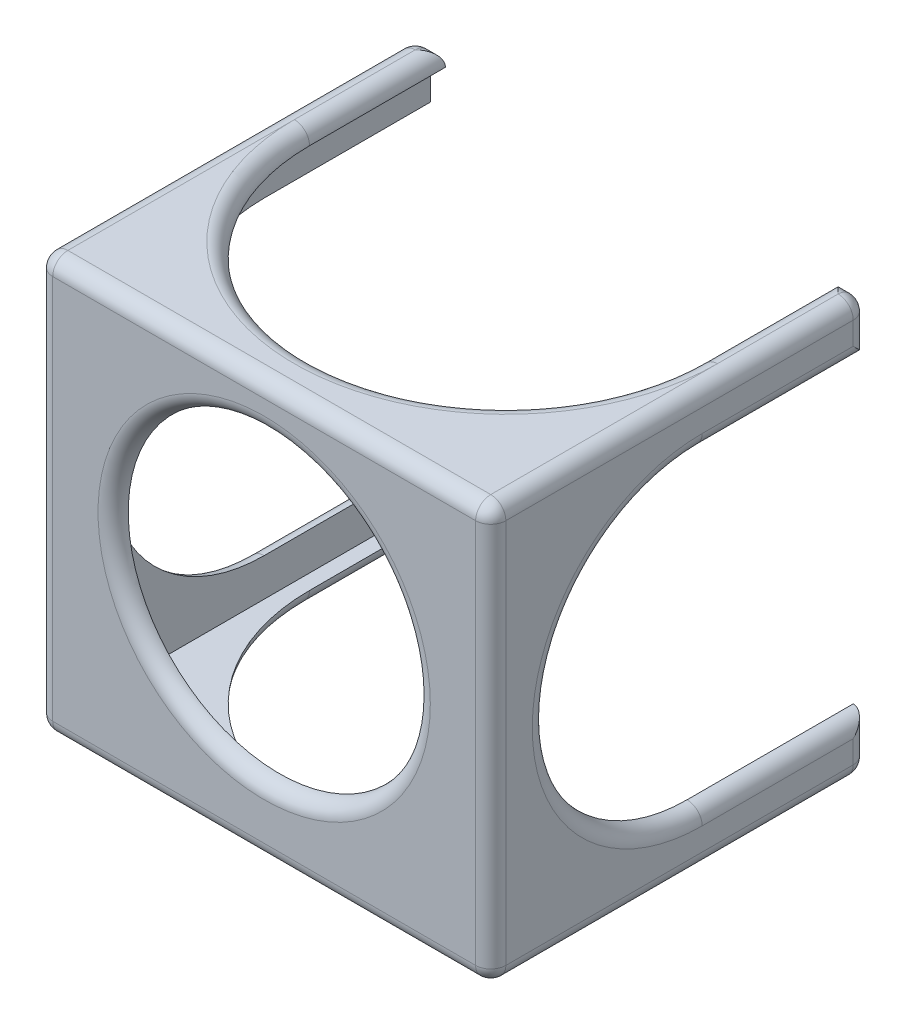
SolidWorks part; units mm, degrees
ref_plane "前视基准面" through (0, 0, 0) normal (0, 0, 1) x (1, 0, 0)
ref_plane "上视基准面" through (0, 0, 0) normal (0, 1, 0) x (1, 0, 0)
ref_plane "右视基准面" through (0, 0, 0) normal (1, 0, 0) x (0, 0, -1)
sketch "草图1" plane through (0, 0, 0) normal (0, 0, 1) x (1, 0, 0)
  line L1 (0, 0) -> (60, 0)
  line L2 (0, 0) -> (0, -55)
  line L3 (0, -55) -> (60, -55)
  line L4 (60, 0) -> (60, -55)
  circle A0 centre (30, -26) radius 20
extrude "凸台-拉伸1" add sketch "草图1" along normal blind 2
sketch "草图2" plane through (0, 0, 0) normal (0, 0, -1) x (-1, 0, 0)
  line L0 (-60, 0) -> (0, 0) construction
  line L1 (-60, 0) -> (0, 0)
  line L2 (-60, 0) -> (-60, -55)
  line L3 (-60, -55) -> (0, -55)
  line L4 (0, 0) -> (0, -55)
  line L5 (-2, -2) -> (-2, -53)
  line L6 (-58, -53) -> (-2, -53)
  line L7 (-58, -2) -> (-58, -53)
  line L8 (-58, -2) -> (-2, -2)
  dimension "D1" = 2
extrude "凸台-拉伸2" add sketch "草图2" along normal blind 48
sketch "草图3" plane through (0, -55, 0) normal (0, -1, 0) x (1, 0, 0)
  line L0 (30, -48) -> (4, -48)
  line L1 (60, -48) -> (0, -48) construction
  line L2 (4, -48) -> (4, -30)
  line L3 (4, -30) -> (30, -30) construction
  line L4 (56, -30) -> (56, -48)
  line L5 (30, -48) -> (56, -48)
  arc A0 (56, -30) -> (4, -30) centre (30, -30) ccw
extrude "切除-拉伸1" cut sketch "草图3" against normal up to surface (55 mm away) up to face at (30, 0, -23)
sketch "草图4" plane through (0, 0, 0) normal (-1, 0, 0) x (0, 0, 1)
  line L0 (-48, -27.5) -> (-26, -27.5) construction
  line L1 (-48, -55) -> (-48, 0) construction
  line L2 (-26, -7) -> (-48, -7)
  line L3 (-48, -7) -> (-48, -48)
  line L4 (-48, -48) -> (-26, -48)
  arc A0 (-26, -48) -> (-26, -7) centre (-26, -27.5) ccw
extrude "切除-拉伸2" cut sketch "草图4" against normal up to surface (60 mm away) up to face at (60, -27.5, -23)
fillet "圆角1" radius 2 29 edges at (56, 0, -39) (58, 0, -48) (2, 0, -48) (4, 0, -39) (30, 0, -4) (0, -7, -37) (0, -3.5, -48) (0, 0, -23) (0, -51.5, -48) (0, -48, -37) (0, -27.5, -5.5) (50, -26, 2) (30, 0, 2) (0, -27.5, 2) (60, -27.5, 2) (60, 0, -23) (60, -3.5, -48) (60, -7, -37) (60, -27.5, -5.5) (60, -48, -37) (60, -51.5, -48) (0, -55, -23) (30, -55, 2) (60, -55, -23) (58, -55, -48) (56, -55, -39) (30, -55, -4) (4, -55, -39) (2, -55, -48)
